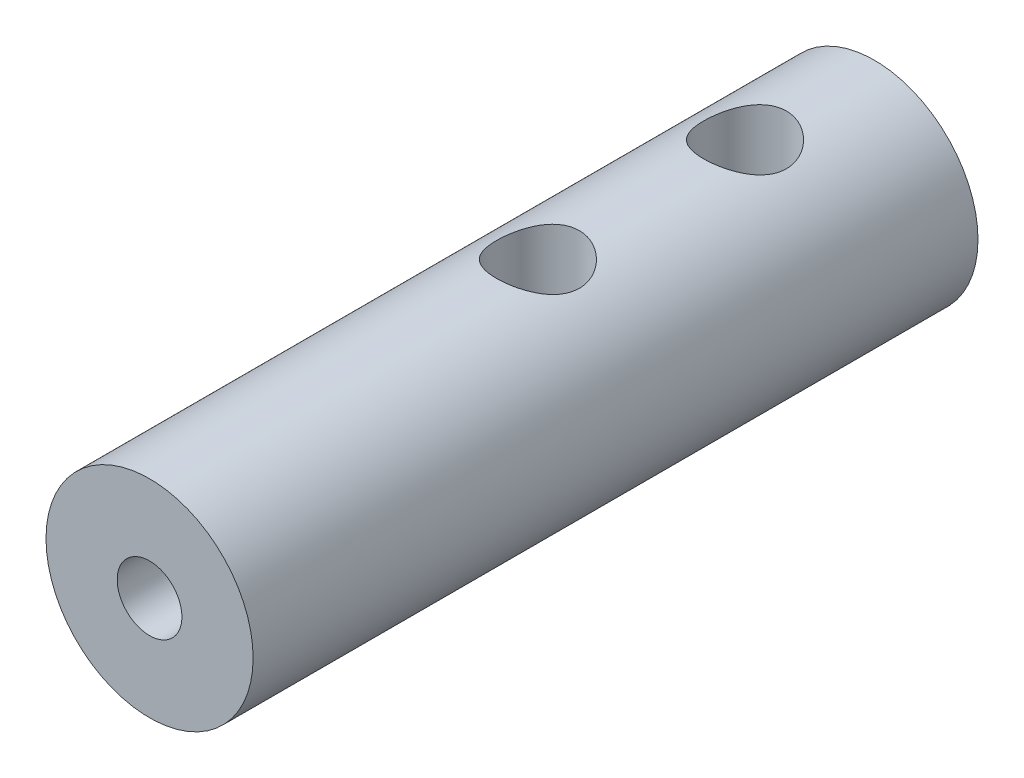
SolidWorks part; units mm, degrees
material "6061 合金"
ref_plane "正面" through (0, 0, 0) normal (0, 0, 1) x (1, 0, 0)
ref_plane "平面" through (0, 0, 0) normal (0, 1, 0) x (1, 0, 0)
ref_plane "右側面" through (0, 0, 0) normal (1, 0, 0) x (0, 0, -1)
sketch "断面" plane through (0, 0, 0) normal (0, 0, 1) x (1, 0, 0)
  circle A0 centre (0, 0) radius 4
  dimension "D1" = 8
extrude "軸全長" add sketch "断面" along normal blind 28
ref_axis "中心軸" through (0, 0, 28) along (0, 0, -1)
ref_plane "上面" through (0, 4, 0) normal (0, 1, 0) x (1, 0, 0)
sketch "上面穴スケッチ" plane through (0, 4, 0) normal (0, 1, 0) x (1, 0, 0)
  line L0 (0, -28) -> (0, 0) construction
  line L1 (4, 0) -> (-4, 0) construction
  circle A0 centre (0, -5) radius 1.6
  circle A1 centre (0, -13) radius 1.6
  dimension "D1" = 5
  dimension "D2" = 3.2
  dimension "D3" = 8
extrude "上面穴貫通" cut sketch "上面穴スケッチ" against normal through all
sketch "上面キー溝スケッチ" plane through (0, 4, 0) normal (0, 1, 0) x (1, 0, 0)
  line L0 (0, -30) -> (0, -50) construction
  line L1 (0, -28) -> (0, 0) construction
  line L2 (1.5, -30) -> (1.5, -50)
  line L3 (-1.5, -30) -> (-1.5, -50)
  line L4 (4, 0) -> (-4, 0) construction
  arc A0 (1.5, -30) -> (-1.5, -30) centre (0, -30) ccw
  arc A1 (-1.5, -50) -> (1.5, -50) centre (0, -50) ccw
  point P5 (0, -40)
  dimension "D1" = 3
  dimension "D2" = 30
  dimension "D3" = 20
extrude "上面キー溝1.6mm" [suppressed] cut sketch "上面キー溝スケッチ" against normal blind 1.6
sketch "上面Dカットスケッチ" plane through (0, 4, 0) normal (0, 1, 0) x (1, 0, 0)
  line L0 (-4, 0) -> (-4, -28) construction
  line L1 (4, -28) -> (-4, -28)
  line L2 (4, -28) -> (4, -18)
  line L3 (4, -18) -> (-4, -18)
  line L4 (-4, -28) -> (-4, -18)
  dimension "D1" = 10
extrude "上面Dカット1mm" [suppressed] cut sketch "上面Dカットスケッチ" against normal blind 1
sketch "Eリング溝スケッチ" plane through (0, 0, 0) normal (0, 1, 0) x (1, 0, 0)
  line L0 (4, -28) -> (4, 0) construction
  line L1 (4, -1) -> (3, -1)
  line L2 (4, -1) -> (4, -2)
  line L3 (4, -2) -> (3, -2)
  line L4 (3, -1) -> (3, -2)
  line L5 (4, 0) -> (-4, 0) construction
  dimension "D1" = 1
  dimension "D2" = 1
revolve "Eリング溝カット" [suppressed] cut sketch "Eリング溝スケッチ" angle 360 about axis through (0, 0, 28) along (0, 0, -1)
sketch "ｽｹｯﾁ1" plane through (0, 0, 28) normal (0, 0, 1) x (1, 0, 0)
  circle A0 centre (0, 0) radius 1.25
  dimension "D1" = 2.5
extrude "ｶｯﾄ - 押し出し1" cut sketch "ｽｹｯﾁ1" against normal blind 8
